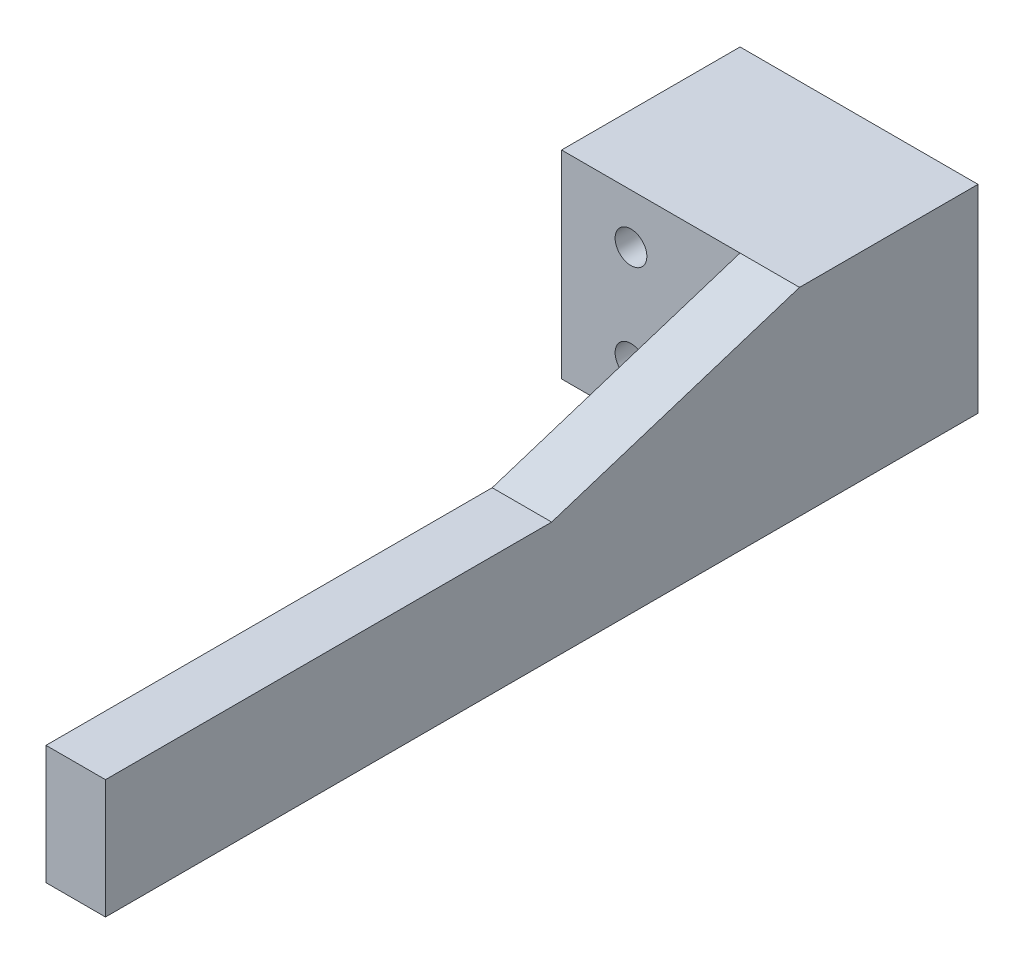
SolidWorks part; units mm, degrees
ref_plane "Front Plane" through (0, 0, 0) normal (0, 0, 1) x (1, 0, 0)
ref_plane "Top Plane" through (0, 0, 0) normal (0, 1, 0) x (1, 0, 0)
ref_plane "Right Plane" through (0, 0, 0) normal (1, 0, 0) x (0, 0, -1)
sketch "Sketch1" plane through (0, 0, 0) normal (0, 0, 1) x (1, 0, 0)
  line L1 (-12, -10) -> (12, -10)
  line L2 (-12, -10) -> (-12, 10)
  line L3 (-12, 10) -> (12, 10)
  line L4 (12, -10) -> (12, 10)
  line L5 (-12, -10) -> (12, 10) construction
  line L6 (-12, 10) -> (12, -10) construction
  circle A0 centre (-5, 5) radius 1.6
  circle A1 centre (-5, -5) radius 1.6
  point P0 (0, 0)
  dimension "D6" = 3.2
  dimension "D7" = 3.2
  dimension "D1" = 24
  dimension "D2" = 20
  dimension "D3" = 10
  dimension "D4" = 5
  dimension "D5" = 7
extrude "Boss-Extrude1" add sketch "Sketch1" along normal blind 18
sketch "Sketch2" plane through (12, 0, 0) normal (1, 0, 0) x (0, 0, -1)
  line L0 (-18, -10) -> (-18, 10) construction
  line L1 (-18, 2) -> (-88, 2)
  line L2 (-18, 2) -> (-18, -10)
  line L3 (-18, -10) -> (-88, -10)
  line L4 (-88, 2) -> (-88, -10)
  line L5 (-18, -10) -> (0, -10) construction
  line L6 (-18, 10) -> (-43, 2)
  line M6 (-18, 10) -> (-18, -10)
  dimension "D1" = 70
  dimension "D2" = 12
  dimension "D3" = 25
extrude "Boss-Extrude2" add sketch "Sketch2" against normal blind 6 contours L6 L1 M6 | L1 L4 L3 L2 region at (12, 4.6667, 26.3333)
ref_plane "Plane1" through (0, -7.5, 0) normal (0, -1, 0) x (-1, 0, 0)
sketch "Sketch3" plane through (0, -7.5, 0) normal (0, -1, 0) x (-1, 0, 0)
  line L0 (-6, -18) -> (-6, -88) construction
  line L1 (-6, -88) -> (-12, -88) construction
  line L2 (12, -9) -> (25.0759, -9) construction
  line L3 (12, -18) -> (12, 0) construction
  circle A0 centre (-6, -83) radius 2.5
  circle A1 centre (-6, -65) radius 2.5
  circle A2 centre (40.6396, -74) radius 45 construction
  point P8 (-9, -88)
  dimension "D1" = 5
  dimension "D2" = 5
  dimension "D3" = 5
  dimension "D5" = 90
  dimension "D4" = 65
extrude "Boss-Extrude3" add sketch "Sketch3" against normal blind 7
fillet "Fillet1" radius 1 4 edges at (6, -4, 85.5) (6, -4, 80.5) (6, -4, 67.5) (6, -4, 62.5)
chamfer "Chamfer1" distance 2.5 angle 45 4 edges at (6, -7.5, 83) (6, -7.5, 65) (6, -0.5, 65) (6, -0.5, 83)
